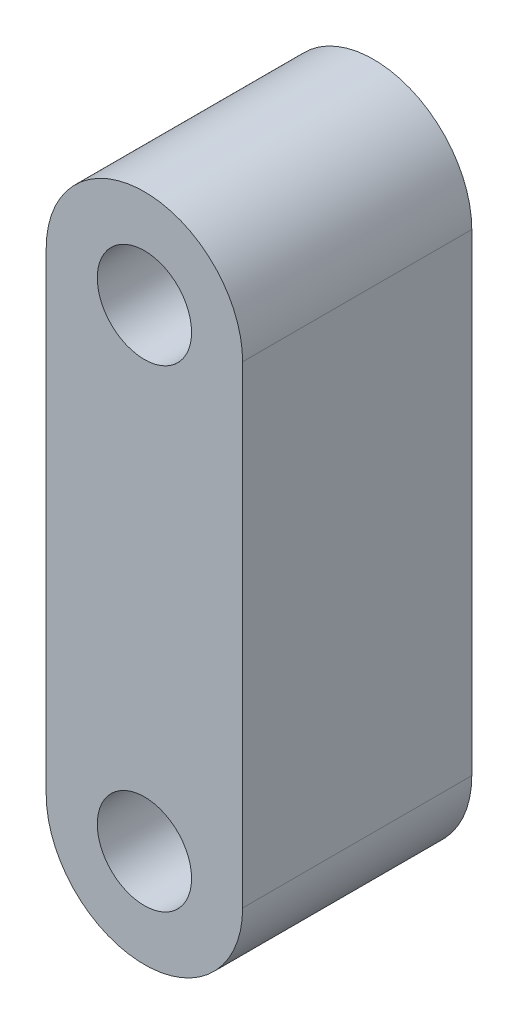
SolidWorks part; units mm, degrees
ref_plane "Front Plane" through (0, 0, 0) normal (0, 0, 1) x (1, 0, 0)
ref_plane "Top Plane" through (0, 0, 0) normal (0, 1, 0) x (1, 0, 0)
ref_plane "Right Plane" through (0, 0, 0) normal (1, 0, 0) x (0, 0, -1)
sketch "Sketch1" plane through (0, 0, 0) normal (0, 0, 1) x (1, 0, 0)
  line L0 (0, 22.9362) -> (0, 0) construction
  line L1 (0, 22.9362) -> (0, 0) construction
  line L2 (4.7625, 22.9362) -> (4.7625, 0)
  line L3 (-4.7625, 22.9362) -> (-4.7625, 0)
  circle A0 centre (0, 0) radius 2.286
  circle A1 centre (0, 22.9362) radius 2.286
  arc A2 (4.7625, 22.9362) -> (-4.7625, 22.9362) centre (0, 22.9362) ccw
  arc A3 (-4.7625, 0) -> (4.7625, 0) centre (0, 0) ccw
  point P5 (0, 11.4681)
  dimension "D1" = 4.572
  dimension "D3" = 4.7625
  dimension "D2" = 22.9362
extrude "Boss-Extrude1" add sketch "Sketch1" along normal blind 11.1125
sketch "Sketch2" plane through (0, 0, 11.1125) normal (0, 0, 1) x (1, 0, 0)
  line L0 (-4.7625, 22.9362) -> (-4.7625, 0) construction
  circle A0 centre (-16.67, 11.4681) radius 14.2875
  point P4 (-4.7625, 11.4681)
  dimension "D2" = 28.575
  dimension "D1" = 16.67
extrude "Cut-Extrude1" [suppressed] cut sketch "Sketch2" against normal through all
fillet "Fillet1" [suppressed] radius 4.7625
